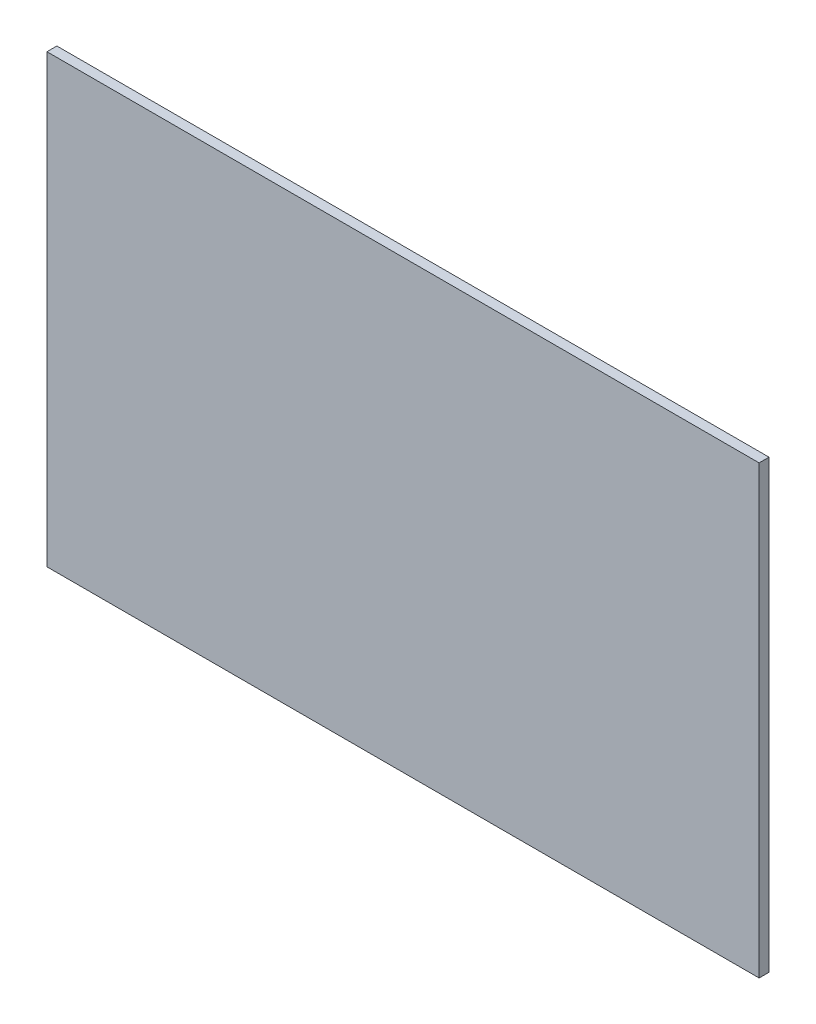
SolidWorks part; units mm, degrees
material "MDF"
ref_plane "Front Plane" through (0, 0, 0) normal (0, 0, 1) x (1, 0, 0)
ref_plane "Top Plane" through (0, 0, 0) normal (0, 1, 0) x (1, 0, 0)
ref_plane "Right Plane" through (0, 0, 0) normal (1, 0, 0) x (0, 0, -1)
sketch "Sketch1" plane through (0, 0, 0) normal (0, 0, 1) x (1, 0, 0)
  line L1 (-228.0888, 0) -> (228.0888, 0)
  line L2 (-228.0888, 0) -> (-228.0888, -285.75)
  line L3 (-228.0888, -285.75) -> (228.0888, -285.75)
  line L4 (228.0888, 0) -> (228.0888, -285.75)
  line L5 (58.5462, -285.75) -> (228.0888, -285.75) construction
  line L7 (228.0888, -3.175) -> (228.0888, -412.75) construction
  line L8 (228.0888, -412.75) -> (228.0888, -285.75) construction
  line L9 (-228.0888, -3.175) -> (-228.0888, -412.75) construction
  line L11 (-209.0388, 0) -> (-228.0888, 0) construction
  point P5 (228.0888, -285.75)
  point P7 (228.0888, -285.75)
  point P12 (0, 0)
  point P14 (0, 0)
  point P15 (-223.6488, -5.9318)
extrude "Boss-Extrude1" add sketch "Sketch1" along normal blind 6.35
